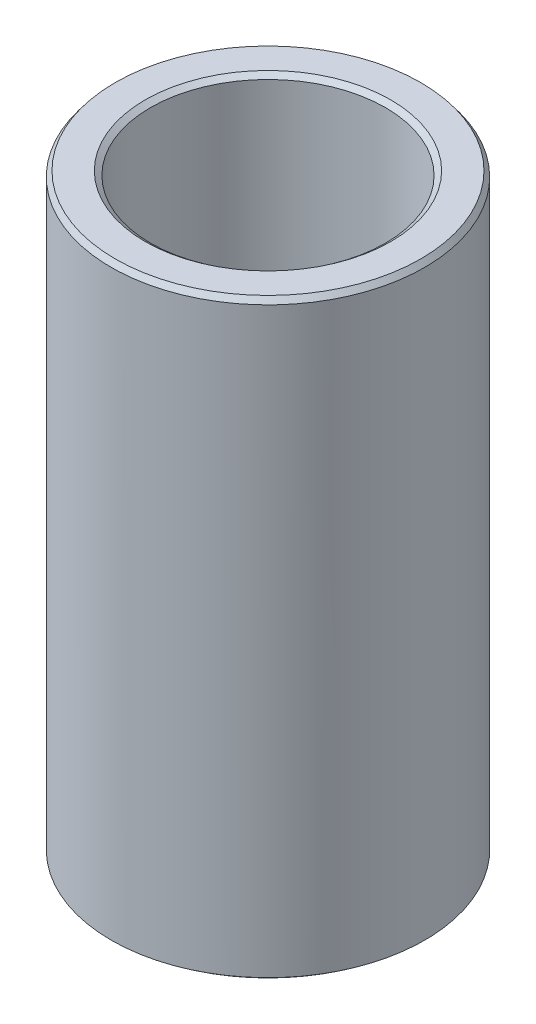
SolidWorks part; units mm, degrees
ref_plane "Front Plane" through (0, 0, 0) normal (0, 0, 1) x (1, 0, 0)
ref_plane "Top Plane" through (0, 0, 0) normal (0, 1, 0) x (1, 0, 0)
ref_plane "Right Plane" through (0, 0, 0) normal (1, 0, 0) x (0, 0, -1)
sketch "Sketch1" plane through (0, 0, 0) normal (0, 1, 0) x (1, 0, 0)
  circle A0 centre (0, 0) radius 55
  dimension "SLEEVE_OD" = 110
extrude "Boss-Extrude1" add sketch "Sketch1" along normal blind 207.6956
sketch "Sketch2" plane through (0, 0, 0) normal (0, 1, 0) x (1, 0, 0)
  circle A0 centre (0, 0) radius 41.2081
  dimension "BORE_D" = 82.4163
extrude "Cut-Extrude1" cut sketch "Sketch2" along normal through all
chamfer "Chamfer1" distance 1.8726 angle 36.989 4 edges at (0, 207.6956, 41.2081) (0, 0, 41.2081) (0, 0, 55) (0, 207.6956, 55) first distance on face at (0, 207.6956, 41.2081) first distance on face at (0, 0, 41.2081) first distance on face at (0, 207.6956, 55)
